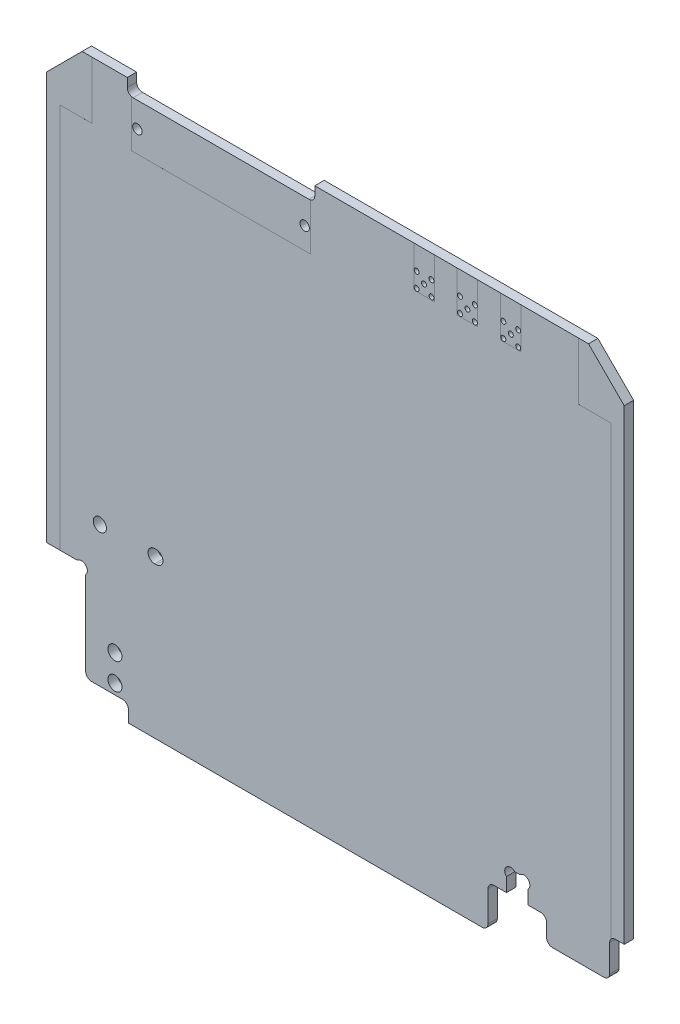
SolidWorks part; units mm, degrees
ref_plane "Front Plane" through (0, 0, 0) normal (0, 0, 1) x (1, 0, 0)
ref_plane "Top Plane" through (0, 0, 0) normal (0, 1, 0) x (1, 0, 0)
ref_plane "Right Plane" through (0, 0, 0) normal (1, 0, 0) x (0, 0, -1)
ref_plane "Plane4" through (0, 0, -0.0125) normal (0, 0, -1) x (-1, 0, 0)
sketch "Sketch1" plane through (0, 0, -0.0125) normal (0, 0, -1) x (-1, 0, 0)
  line L0 (35.3, -50) -> (35.3, -48)
  line L1 (36.3, -47) -> (45.8, -47)
  line L2 (46.8, -46) -> (46.8, -41.4)
  line L3 (47.8, -40.4) -> (49.3, -40.4)
  line L4 (49.3, -40.4) -> (49.3, 39.2)
  line L5 (49.3, 39.2) -> (43.2, 45.3)
  line L6 (43.2, 45.3) -> (35.5, 45.3)
  line L7 (35.5, 45.3) -> (35.5, 43.8)
  line L8 (34.5, 42.8) -> (4.5, 42.8)
  line L9 (3.5, 43.8) -> (3.5, 45.3)
  line L10 (3.5, 45.3) -> (-43.2, 45.3)
  line L11 (-43.2, 45.3) -> (-49.3, 39.2)
  line L12 (-49.3, 39.2) -> (-49.3, -40.4)
  line L13 (-49.3, -40.4) -> (-47.8, -40.4)
  line L14 (-46.8, -41.4) -> (-46.8, -46)
  line L15 (-45.8, -47) -> (-36.3, -47)
  line L16 (-35.3, -48) -> (-35.3, -50)
  line L17 (-35.3, -50) -> (35.3, -50)
  line L18 (0, -50) -> (0, 45.3) construction
  line L19 (19.5, 42.8) -> (19.5, 25.5258) construction
  line L20 (-13.87, 41.37) -> (-16.41, 38.83) construction
  line L21 (-21.27, 41.37) -> (-23.81, 38.83) construction
  line L22 (-28.67, 41.37) -> (-31.21, 38.83) construction
  arc A0 (35.3, -48) -> (36.3, -47) centre (36.3, -48) cw
  arc A1 (45.8, -47) -> (46.8, -46) centre (45.8, -46) ccw
  arc A2 (46.8, -41.4) -> (47.8, -40.4) centre (47.8, -41.4) cw
  arc A3 (35.5, 43.8) -> (34.5, 42.8) centre (34.5, 43.8) cw
  arc A4 (4.5, 42.8) -> (3.5, 43.8) centre (4.5, 43.8) cw
  arc A5 (-47.8, -40.4) -> (-46.8, -41.4) centre (-47.8, -41.4) cw
  arc A6 (-46.8, -46) -> (-45.8, -47) centre (-45.8, -46) ccw
  arc A7 (-36.3, -47) -> (-35.3, -48) centre (-36.3, -48) cw
  circle A8 centre (-21.27, 41.37) radius 0.425
  circle A9 centre (-23.81, 41.37) radius 0.425
  circle A10 centre (-22.54, 40.1) radius 0.425
  circle A11 centre (-13.87, 41.37) radius 0.425
  circle A12 centre (-23.81, 38.83) radius 0.425
  circle A13 centre (-16.41, 41.37) radius 0.425
  circle A14 centre (-15.14, 40.1) radius 0.425
  circle A15 centre (-21.27, 38.83) radius 0.425
  circle A16 centre (-28.67, 41.37) radius 0.425
  circle A17 centre (-31.21, 41.37) radius 0.425
  circle A18 centre (-16.41, 38.83) radius 0.425
  circle A19 centre (-29.94, 40.1) radius 0.425
  circle A20 centre (-31.21, 38.83) radius 0.425
  circle A21 centre (-28.67, 38.83) radius 0.425
  circle A22 centre (33.775, 38.54) radius 0.8
  circle A23 centre (5.225, 38.54) radius 0.8
  circle A24 centre (-13.87, 38.83) radius 0.425
  point P35 (-15.14, 40.1)
  dimension "D7" = 2.5
  dimension "D8" = 1.6
  dimension "D9" = 14.275
  dimension "D10" = 4.26
  dimension "D11" = 1
  dimension "D12" = 1
  dimension "D13" = 1
  dimension "D14" = 1
  dimension "D15" = 1
  dimension "D16" = 1
  dimension "D17" = 1
  dimension "D18" = 1
  dimension "D26" = 0.85
  dimension "D1" = 98.6
  dimension "D2" = 95.3
  dimension "D3" = 14
  dimension "D4" = 9.6
  dimension "D5" = 2.5
  dimension "D6" = 3
  dimension "D19" = 14
  dimension "D20" = 2.5
  dimension "D21" = 6.1
  dimension "D22" = 6.1
  dimension "D23" = 32
  dimension "D24" = 2.54
  dimension "D25" = 2.54
  dimension "D28" = 7.4
  dimension "D29" = 3.93
  dimension "D30" = 35.43
  dimension "D31" = 45
  dimension "D32" = 45
  dimension "D33" = 29.8
  dimension "D34" = 50
  dimension "D27" = 3
extrude "Boss-Extrude1" add sketch "Sketch1" against normal blind 1.6
sketch "thermalContacts_lower" plane through (0, 0, -0.0125) normal (0, 0, -1) x (-1, 0, 0)
  line L0 (47, 35.5) -> (47, -41.5) construction
  line L1 (41.5, 35.5) -> (41.5, 41.5) construction
  line L2 (41.5, 35.5) -> (47, 35.5) construction
  line L3 (47, 35.5) -> (47, -41.5)
  line L4 (41.5, 35.5) -> (41.5, 41.5)
  line L5 (41.5, 35.5) -> (47, 35.5)
  line L6 (-47, 35.5) -> (-47, -41.5) construction
  line L7 (-41.5, 35.5) -> (-47, 35.5) construction
  line L8 (-41.5, 35.5) -> (-41.5, 41.5) construction
  line L9 (-47, 35.5) -> (-47, -41.5)
  line L10 (-41.5, 35.5) -> (-47, 35.5)
  line L11 (-41.5, 35.5) -> (-41.5, 41.5)
  line L12 (-41.5, 41.5) -> (-41.5, 47) construction
  line L13 (-41.5, 41.5) -> (-49.5, 41.5) construction
  line L14 (-41.5, 41.5) -> (-41.5, 47)
  line L15 (-41.5, 41.5) -> (-49.5, 41.5) construction
  line L16 (41.5, 41.5) -> (41.5, 47) construction
  line L17 (41.5, 41.5) -> (49.5, 41.5) construction
  line L18 (41.5, 41.5) -> (41.5, 47)
  line L19 (41.5, 41.5) -> (49.5, 41.5) construction
  line L20 (47, -41.5) -> (59.8273, -41.5)
  line L21 (59.8273, -41.5) -> (59.8273, 47)
  line L22 (-56.1922, 47) -> (-41.5, 47)
  line L23 (41.5, 47) -> (59.8273, 47)
  line L24 (-56.1922, 47) -> (-56.1922, -41.5)
  line L25 (-47, -41.5) -> (-56.1922, -41.5)
sketch "thermalContacts_upper" plane through (0, 0, 1.5875) normal (0, 0, 1) x (1, 0, 0)
  line L3 (-47, 35.5) -> (-47, -41.5)
  line L4 (-41.5, 35.5) -> (-41.5, 41.5)
  line L5 (-41.5, 35.5) -> (-47, 35.5)
  line L9 (47, 35.5) -> (47, -41.5)
  line L10 (41.5, 35.5) -> (47, 35.5)
  line L11 (41.5, 35.5) -> (41.5, 41.5)
  line L14 (41.5, 41.5) -> (41.5, 47)
  line L15 (41.5, 41.5) -> (49.5, 41.5) construction
  line L18 (-41.5, 41.5) -> (-41.5, 47)
  line L19 (-41.5, 41.5) -> (-49.5, 41.5) construction
  line L20 (47, -41.5) -> (59.8273, -41.5)
  line L21 (59.8273, -41.5) -> (59.8273, 47)
  line L22 (59.8273, 47) -> (41.5, 47)
  line L23 (-41.5, 47) -> (-56.1922, 47)
  line L24 (-56.1922, 47) -> (-56.1922, -41.5)
  line L25 (-56.1922, -41.5) -> (-47, -41.5)
extrude "Cut-Extrude1" cut sketch "thermalContacts_lower" against normal blind 0.0001
extrude "Cut-Extrude2" cut sketch "thermalContacts_upper" against normal blind 0.0001
sketch "partFootprints" plane through (0, 0, 1.5875) normal (0, 0, 1) x (1, 0, 0)
  line L0 (-34.74, 34.84) -> (-34.74, 42.8292)
  line L1 (-4.26, 34.84) -> (-34.74, 34.84)
  line L2 (-41.5, 45.3) -> (-35.5, 45.3) construction
  line L3 (-36.1132, 45.3) -> (-39.5054, 45.3) construction
  line L4 (-4.26, 34.84) -> (-4.26, 42.8292)
  line L5 (-49.3, -40.4) -> (-49.3, 39.2) construction
  line L6 (13.39, 45.3) -> (13.39, 38.35)
  line L7 (13.39, 38.35) -> (16.89, 38.35)
  line L8 (16.89, 38.35) -> (16.89, 45.3)
  line L9 (16.89, 45.3) -> (13.39, 45.3)
  line L10 (20.79, 45.3) -> (20.79, 38.35)
  line L11 (20.79, 38.35) -> (24.29, 38.35)
  line L12 (24.29, 38.35) -> (24.29, 45.3)
  line L13 (24.29, 45.3) -> (20.79, 45.3)
  line L14 (28.19, 45.3) -> (28.19, 38.35)
  line L15 (28.19, 38.35) -> (31.69, 38.35)
  line L16 (31.69, 38.35) -> (31.69, 45.3)
  line L17 (31.69, 45.3) -> (28.19, 45.3)
  line L19 (14.12, 38.35) -> (16.16, 38.35) construction
  line L20 (-34.74, 42.8292) -> (-4.26, 42.8292)
  line L21 (-3.5, 45.3) -> (41.5, 45.3) construction
  line L22 (14.12, 38.35) -> (16.16, 38.35) construction
  line L23 (13.39, 41.85) -> (13.39, 38.35) construction
  line L24 (16.89, 41.85) -> (16.89, 38.35) construction
  line L25 (13.39, 41.85) -> (13.39, 38.35) construction
  line L26 (16.89, 41.85) -> (16.89, 38.35) construction
  arc A0 (-35.5, 43.8) -> (-34.5, 42.8) centre (-34.5, 43.8) ccw construction
  arc A1 (-4.5, 42.8) -> (-3.5, 43.8) centre (-4.5, 43.8) ccw construction
  dimension "D1" = 10.46
  dimension "D2" = 14.56
  dimension "D3" = 30.48
  dimension "D7" = 7.4
  dimension "D6" = 3
extrude "Cut-Extrude3" cut sketch "partFootprints" against normal blind 0.0001
sketch "Sketch2" plane through (0, 0, 1.5875) normal (0, 0, 1) x (1, 0, 0)
  line L0 (35.1, -50) -> (35.1, -37.5518) construction
  line L1 (35.3, -50) -> (-35.3, -50) construction
  line L2 (27, -50) -> (27, -36.9095) construction
  line L3 (35.3, -48) -> (35.3, -50) construction
  line L4 (29.2, -42.8) -> (29.2, -40.4142)
  line L5 (27, -39) -> (35.1, -39) construction
  line L6 (30.6142, -39) -> (31.4858, -39)
  line L7 (32.9, -40.4142) -> (32.9, -42.8)
  line L8 (26.05, -50) -> (36.05, -50)
  line L9 (30.6142, -39) -> (31.4858, -39) construction
  line L10 (26.05, -50) -> (26.05, -42.8)
  line L11 (26.05, -42.8) -> (29.2, -42.8)
  line L12 (31.05, -39) -> (31.05, -50) construction
  line L13 (36.05, -42.8) -> (32.9, -42.8)
  line L14 (36.05, -50) -> (36.05, -42.8)
  line L15 (48.0683, 27.2) -> (36.7758, 27.2) construction
  line L16 (48.0683, 35.5) -> (35.6387, 35.5) construction
  line L17 (42.1, 29.55) -> (39.0071, 29.55) construction
  line L18 (38.3, 35.5) -> (38.3, 27.2) construction
  line L19 (38.3, 30.2571) -> (38.3, 32.4429) construction
  line L20 (39.0071, 33.15) -> (42.1, 33.15) construction
  line L21 (49.3, 29.1) -> (49.3, 33.6) construction
  line L22 (38.3, 30.2571) -> (38.3, 32.4429) construction
  line L23 (49.3, 29.1) -> (42.1, 29.1) construction
  line L24 (42.1, 29.1) -> (42.1, 29.55) construction
  line L25 (38.3, 31.35) -> (49.3, 31.35) construction
  line L26 (42.1, 33.6) -> (42.1, 33.15) construction
  line L27 (49.3, 33.6) -> (42.1, 33.6) construction
  line L28 (49.3, -40.4) -> (49.3, 39.2) construction
  line L30 (31.69, 45.3) -> (41.5, 45.3) construction
  arc A0 (29.2, -40.4142) -> (30.6142, -39) centre (29.9071, -39.7071) cw
  arc A1 (31.4858, -39) -> (32.9, -40.4142) centre (32.1929, -39.7071) cw
  arc A2 (39.0071, 29.55) -> (38.3, 30.2571) centre (38.6536, 29.9036) cw construction
  arc A3 (38.3, 32.4429) -> (39.0071, 33.15) centre (38.6536, 32.7964) cw construction
  point P8 (35.3, -49)
  point P39 (38.3, 31.35)
  point P46 (38.3, 31.35)
  point P47 (38.3, 29.55)
  point P48 (38.3, 33.15)
  point P57 (31.05, -39)
  point P59 (32.9, -39)
  point P60 (29.2, -39)
  dimension "D5" = 1
  dimension "D8" = 0.5
  dimension "D1" = 0.2
  dimension "D2" = 8.3
  dimension "D3" = 3.7
  dimension "D4" = 11
  dimension "D6" = 3.8
  dimension "D7" = 10
  dimension "D9" = 3.6
  dimension "D10" = 11
  dimension "D11" = 3.8
  dimension "D12" = 4.5
  dimension "D13" = 9.8
  dimension "D14" = 8.3
extrude "Cut-Extrude4" cut sketch "Sketch2" against normal through all
sketch "Sketch3" plane through (0, 0, 1.5875) normal (0, 0, 1) x (1, 0, 0)
  line L0 (45.8, -47) -> (36.3, -47) construction
  line L1 (31.741, -47) -> (39.5208, -47)
  line L2 (31.741, -47) -> (31.741, -52.1552)
  line L3 (31.741, -52.1552) -> (39.5208, -52.1552)
  line L4 (39.5208, -47) -> (39.5208, -52.1552)
extrude "Cut-Extrude5" cut sketch "Sketch3" against normal blind 10
fillet "Fillet1" radius 1 4 edges at (36.05, -42.8, 0.7875) (26.05, -42.8, 0.7875) (36.05, -47, 0.7875) (26.05, -50, 0.7875)
sketch "Sketch4" plane through (0, 0, 1.5875) normal (0, 0, 1) x (1, 0, 0)
  line L0 (-36.3, -47) -> (-45.8, -47) construction
  line L1 (-51.3808, -30.3) -> (-44.0142, -30.3)
  line L2 (-51.3808, -30.3) -> (-51.3808, -47)
  line L3 (-51.3808, -47) -> (-42.6, -47)
  line L4 (-42.6, -31.7142) -> (-42.6, -47)
  line L5 (-42.8, -36) -> (-42.8, -47.5929) construction
  line L6 (-44.0142, -30.3) -> (-42.6, -30.3) construction
  line L7 (-42.6, -30.3) -> (-42.6, -31.7142) construction
  arc A0 (-44.0142, -30.3) -> (-42.6, -31.7142) centre (-43.3071, -31.0071) cw
  point P11 (-42.6, -30.3)
  dimension "D1" = 1
  dimension "D2" = 0.2
  dimension "D3" = 16.7
extrude "Cut-Extrude6" cut sketch "Sketch4" against normal through all
fillet "Fillet2" radius 1 1 edges at (-42.6, -47, 0.7875)
sketch "Sketch5" plane through (0, 0, 1.5875) normal (0, 0, 1) x (1, 0, 0)
  line L0 (-30.525, -24.225) -> (-30.825, -24.225) construction
  line L1 (-30.525, -24.225) -> (-30.825, -24.225)
  line L2 (-30.825, -21.975) -> (-30.525, -21.975) construction
  line L3 (-30.825, -21.975) -> (-30.525, -21.975)
  circle A0 centre (-40.175, -23.1) radius 1.125 construction
  circle A1 centre (-40.175, -23.1) radius 1.125
  arc A2 (-30.825, -21.975) -> (-30.825, -24.225) centre (-30.825, -23.1) ccw construction
  arc A3 (-30.525, -24.225) -> (-30.525, -21.975) centre (-30.525, -23.1) ccw construction
  arc A4 (-30.825, -21.975) -> (-30.825, -24.225) centre (-30.825, -23.1) ccw
  arc A5 (-30.525, -24.225) -> (-30.525, -21.975) centre (-30.525, -23.1) ccw
extrude "Cut-Extrude7" cut sketch "Sketch5" against normal through all
sketch "Sketch6" plane through (0, 0, 1.5875) normal (0, 0, 1) x (1, 0, 0)
  circle A1 centre (-37.6, -40.75) radius 1.2
  circle A2 centre (-37.6, -45.25) radius 1.2 construction
  circle A3 centre (-37.6, -45.25) radius 1.2
  circle A4 centre (-37.6, -40.75) radius 1.2 construction
extrude "Cut-Extrude8" cut sketch "Sketch6" against normal through all
